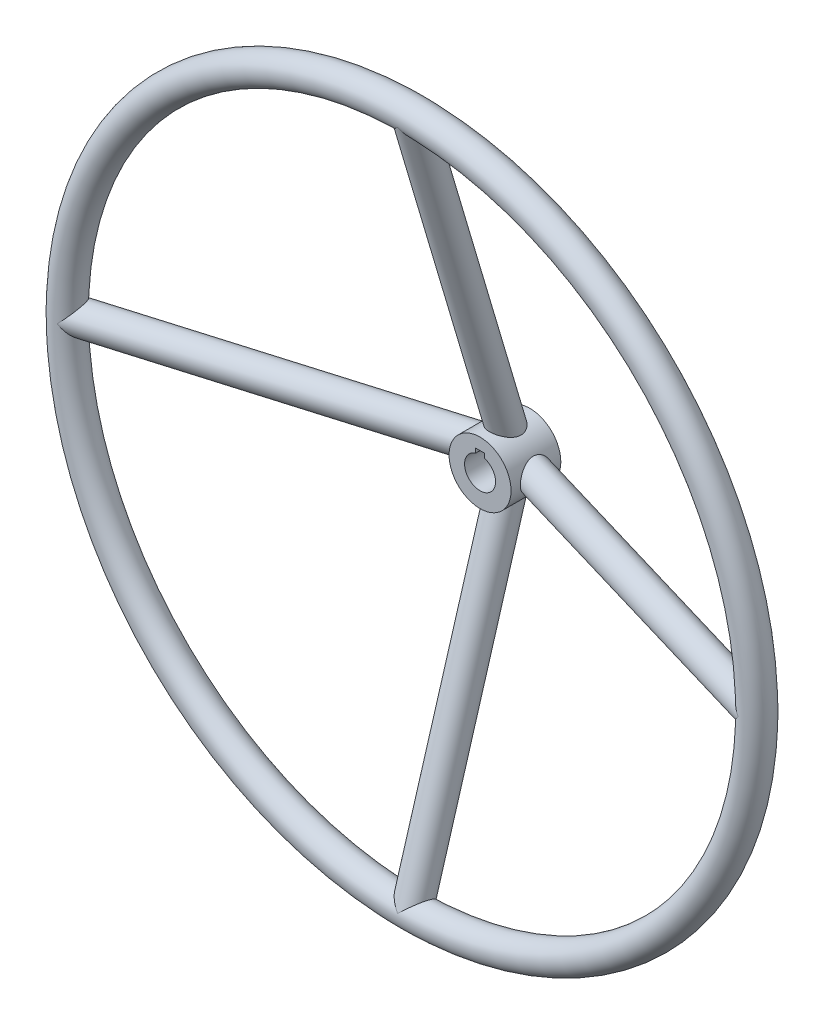
SolidWorks part; units mm, degrees
ref_plane "Front Plane" through (0, 0, 0) normal (0, 0, 1) x (1, 0, 0)
ref_plane "Top Plane" through (0, 0, 0) normal (0, 1, 0) x (1, 0, 0)
ref_plane "Right Plane" through (0, 0, 0) normal (1, 0, 0) x (0, 0, -1)
sketch "Sketch1" plane through (0, 0, 0) normal (1, 0, 0) x (0, 0, -1)
  line L0 (0, 0) -> (-79.9892, 0) construction
  circle A0 centre (0, 311.5) radius 13.5
  circle A1 centre (0, 311.5) radius 10.5
  point P2 (0, 325)
  dimension "D1" = 27
  dimension "D2" = 325
  dimension "D3" = 3
revolve "Revolve1" add sketch "Sketch1" angle 360 about L0
sketch "Sketch3" plane through (0, 0, 0) normal (0, 0, 1) x (1, 0, 0)
  circle A0 centre (0, 0) radius 28
  circle A1 centre (0, 0) radius 14
  dimension "D1" = 28
  dimension "D2" = 56
extrude "Boss-Extrude1" add sketch "Sketch3" along normal blind 45 from offset 106.5 separate body offset against normal yes
sketch "Sketch4" plane through (0, 0, 0) normal (1, 0, 0) x (0, 0, -1)
  line L0 (0, 311.5) -> (84, 28)
  line L1 (106.5, 28) -> (61.5, 28) construction
  circle A3 centre (0, 311.5) radius 13.5
  circle A4 centre (0, 311.5) radius 13.5 construction
  dimension "D2" = 0
sweep "Sweep1" add path "Sketch4" circular profile diameter 27 parameters "D3"=27
sketch "Sketch11" plane through (0, 2.86, 0.8474) normal (0, -0.9588, -0.2841) x (1, 0, 0)
  arc A1 (-8.7579, -76.7661) -> (8.7579, -76.7661) centre (0, -87.0398) ccw construction
  circle A2 centre (0, -87.0398) radius 12
  dimension "D1" = 13.5
  dimension "D2" = 24
extrude "Cut-Extrude1" cut sketch "Sketch11" against normal up to surface (295.6827 mm away) up to face at (0.0203, 311.4879, 0.0408)
sketch "Sketch12" plane through (0, 2.86, 0.8474) normal (0, -0.9588, -0.2841) x (1, 0, 0)
  arc A2 (-10.5218, -81.2699) -> (10.5218, -81.2699) centre (0, -87.0398) ccw
  arc A3 (-10.9662, -80.6199) -> (10.9662, -80.6199) centre (0, -88.4935) ccw
  arc A4 (-10.5218, -81.2699) -> (10.5218, -81.2699) centre (0, -87.0398) ccw
  arc A5 (-10.9662, -80.6199) -> (10.9662, -80.6199) centre (0, -88.4935) ccw
  ellipse E2 centre (0, 10.0674) end of major axis (0, -88.4935) minor radius 28 (-10.9662, -80.6199) -> (-10.5218, -81.2699) ccw
  ellipse E3 centre (0, 10.0674) end of major axis (0, -88.4935) minor radius 28 (10.5218, -81.2699) -> (10.9662, -80.6199) ccw
  ellipse E4 centre (0, 10.0674) end of major axis (0, -88.4935) minor radius 28 (-10.9662, -80.6199) -> (-10.5218, -81.2699) ccw
  ellipse E5 centre (0, 10.0674) end of major axis (0, -88.4935) minor radius 28 (10.5218, -81.2699) -> (10.9662, -80.6199) ccw
  dimension "D1" = 0
extrude "Boss-Extrude2" add sketch "Sketch12" along normal up to surface up to face at (0.0579, 26.928, -76.8634)
pattern_circular "CirPattern1" count 4 over 360 about axis through (0, 0, -106.5) along (0, 0, 1) of "Sweep1", "Cut-Extrude1", "Boss-Extrude2"
sketch "Sketch16" plane through (0, 0, -106.5) normal (0, 0, -1) x (-1, 0, 0)
  line L1 (-3.9688, 13.4257) -> (3.9688, 13.4257)
  line L2 (-3.9688, 13.4257) -> (-3.9688, 17.3944)
  line L3 (-3.9688, 17.3944) -> (3.9688, 17.3944)
  line L4 (3.9688, 13.4257) -> (3.9688, 17.3944)
  circle A0 centre (0, 0) radius 14 construction
  point P7 (0, 13.4257)
  dimension "D1" = 3.9688
  dimension "D2" = 7.9375
extrude "Cut-Extrude2" cut sketch "Sketch16" against normal through all both and the other way through all
